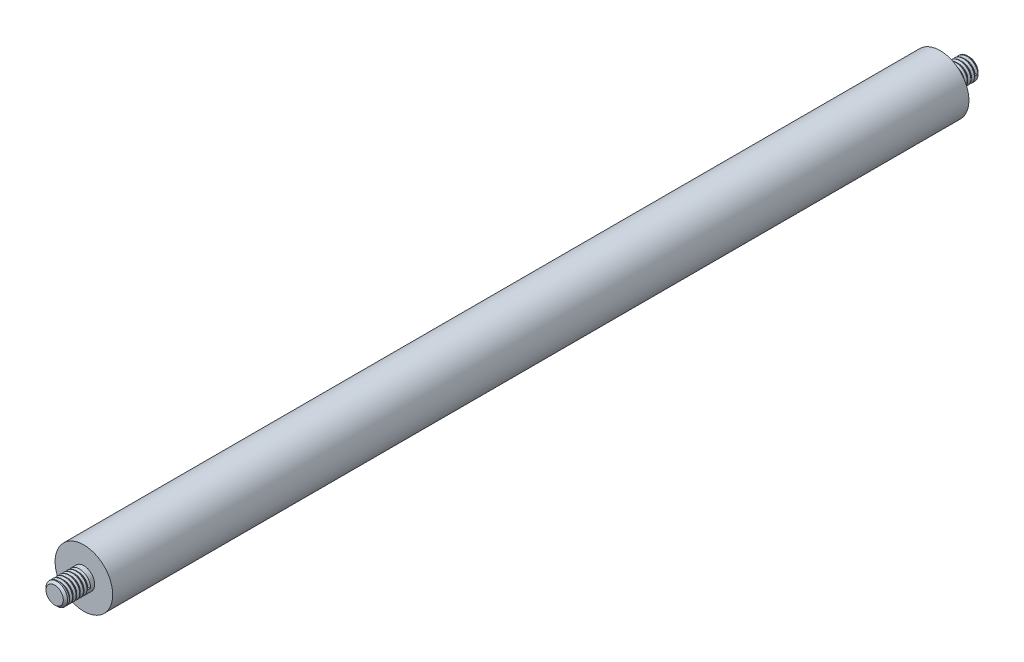
SolidWorks part; units mm, degrees
ref_plane "Front Plane" through (0, 0, 0) normal (0, 0, 1) x (1, 0, 0)
ref_plane "Top Plane" through (0, 0, 0) normal (0, 1, 0) x (1, 0, 0)
ref_plane "Right Plane" through (0, 0, 0) normal (1, 0, 0) x (0, 0, -1)
sketch "Sketch2" plane through (0, 0, 0) normal (0, 0, 1) x (1, 0, 0)
  circle A0 centre (0, 0) radius 12.7
  dimension "D1" = 25.4
extrude "Boss-Extrude1" add sketch "Sketch2" against normal blind 377.698
sketch "Sketch8" plane through (0, 0, 0) normal (1, 0, 0) x (0, 0, -1)
  line L0 (0, 0) -> (-12.8905, 0)
  line L1 (-12.8905, 0) -> (-12.8905, 3.8163)
  line L2 (-12.8905, 3.8163) -> (-11.9443, 4.7625)
  line L3 (0, 0) -> (0, 4.7625)
  line L5 (-11.9443, 4.7625) -> (0, 4.7625)
  dimension "D1" = 4.7625
  dimension "D2" = 3.8163
  dimension "D3" = 135
  dimension "D4" = 11.9443
revolve "Revolve1" add sketch "Sketch8" angle 360 about L0
thread "Thread2" pitch 1.5875 method cut profile "Thread Profile2" start angle 0, offset 0, length 8.763, pitch 1.5875, diameter 9.525
ref_plane "Plane2" through (-4.7625, 0, 11.9443) normal (0, -1, 0) x (-1, 0, 0)
sketch "Thread Profile2" plane through (-4.7625, 0, 11.9443) normal (0, -1, 0) x (-1, 0, 0)
  line L0 (0, 0) -> (0, 1.5875) construction
  line L11 (0, 0) -> (0, 1.3891)
  line L12 (0, 1.3891) -> (-0.8593, 0.893)
  line L13 (-0.8593, 0.893) -> (-0.8593, 0.4961)
  line L15 (-0.8593, 0.4961) -> (0, 0)
  line L17 (-0.8593, 0.6945) -> (0, 0.6945) construction
  point P2 (0, 0)
  dimension "Pitch" = 1.5875
  dimension "Profile_Angle" = 60
  dimension "Profile_Land" = 0.3969
  dimension "Profile_Height" = 0.8593
ref_plane "Plane3" through (0, 0, -188.849) normal (0, 0, 1) x (1, 0, 0)
mirror "Mirror3" about plane through (0, 0, -188.849) normal (0, 0, 1) of "Revolve1"
thread "Thread3" pitch 1.5875 method cut profile "Thread Profile3" start angle 0, offset 0, length 8.763, pitch 1.5875, diameter 9.525
ref_plane "Plane4" through (4.7625, 0, -389.6423) normal (0, -1, 0) x (1, 0, 0)
sketch "Thread Profile3" plane through (4.7625, 0, -389.6423) normal (0, -1, 0) x (1, 0, 0)
  line L0 (0, 0) -> (0, 1.5875) construction
  line L11 (0, 0) -> (0, 1.3891)
  line L12 (0, 1.3891) -> (-0.8593, 0.893)
  line L13 (-0.8593, 0.893) -> (-0.8593, 0.4961)
  line L15 (-0.8593, 0.4961) -> (0, 0)
  line L17 (-0.8593, 0.6945) -> (0, 0.6945) construction
  point P2 (0, 0)
  dimension "Pitch" = 1.5875
  dimension "Profile_Angle" = 60
  dimension "Profile_Land" = 0.3969
  dimension "Profile_Height" = 0.8593
